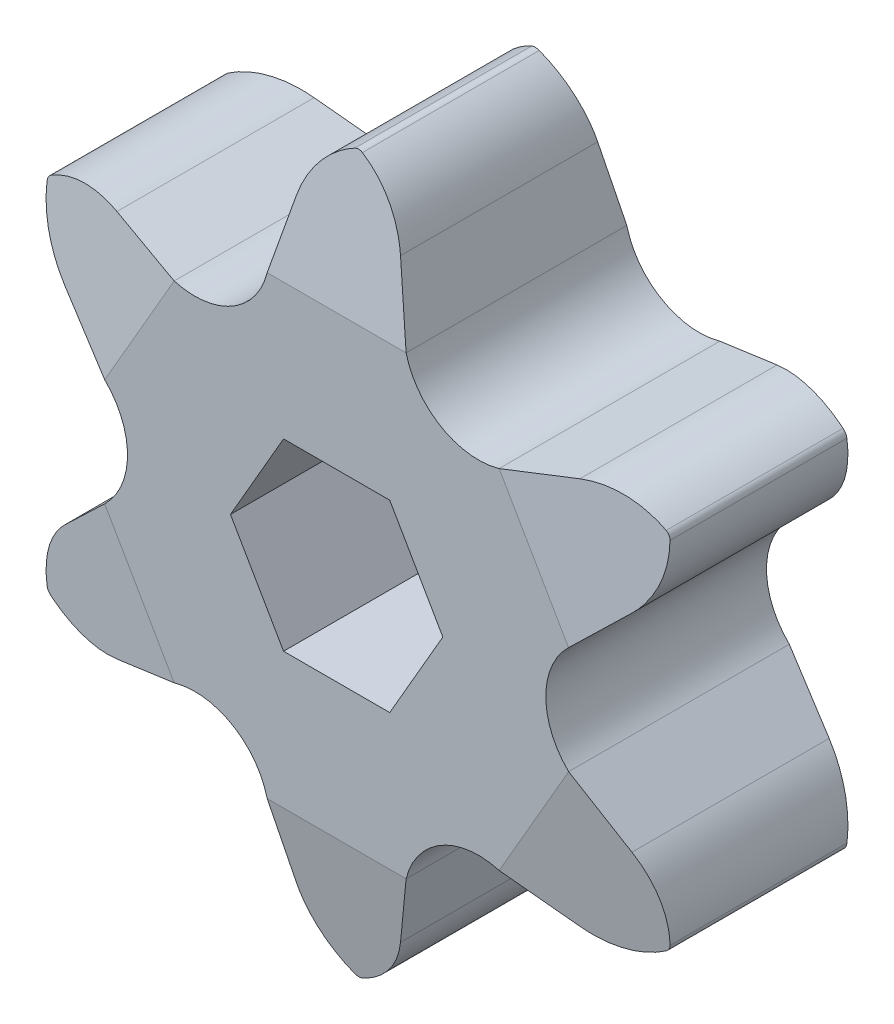
SolidWorks part; units mm, degrees
ref_plane "Front Plane" through (0, 0, 0) normal (0, 0, 1) x (1, 0, 0)
ref_plane "Top Plane" through (0, 0, 0) normal (0, 1, 0) x (1, 0, 0)
ref_plane "Right Plane" through (0, 0, 0) normal (1, 0, 0) x (0, 0, -1)
sketch "Sketch1" plane through (0, 0, 0) normal (0, 0, 1) x (1, 0, 0)
  line L0 (-5.0267, 5.911) -> (-7.4077, 6.5937)
  line L1 (-9.2066, 3.4779) -> (-7.4249, 1.7573)
  line L2 (2.9817, 7.7655) -> (2.3825, 10.1689)
  line L3 (-1.2153, 10.1689) -> (-1.8146, 7.7655)
  line L4 (8.592, 1.7573) -> (10.3738, 3.4779)
  line L5 (8.5749, 6.5937) -> (6.1938, 5.911)
  line L6 (6.1938, -6.1055) -> (8.5749, -6.7882)
  line L7 (10.3738, -3.6724) -> (8.592, -1.9518)
  line L8 (-1.8146, -7.96) -> (-1.2153, -10.3634)
  line L9 (2.3825, -10.3634) -> (2.9817, -7.96)
  line L10 (-7.4249, -1.9518) -> (-9.2066, -3.6724)
  line L11 (-7.4077, -6.7882) -> (-5.0267, -6.1055)
  arc A0 (-7.1314, 1.42) -> (-7.4249, 1.7573) centre (-9.2158, -0.0973) ccw
  arc A1 (-10.0364, 6.1886) -> (-10.1701, 5.9569) centre (-9.8707, 5.9385) ccw
  arc A2 (-4.5879, 5.8255) -> (-1.9599, 7.3427) centre (-4.3161, 8.3892) ccw
  arc A3 (-5.0267, 5.911) -> (-4.5879, 5.8255) centre (-4.3161, 8.3892) ccw
  arc A4 (-7.4077, 6.5937) -> (-10.0364, 6.1886) centre (-8.2829, 3.5417) ccw
  arc A5 (-10.1701, 5.9569) -> (-9.2066, 3.4779) centre (-7.0011, 5.7618) ccw
  arc A6 (-1.9599, 7.3427) -> (-1.8146, 7.7655) centre (-4.3161, 8.3892) ccw
  arc A7 (0.7173, 12.2428) -> (0.4498, 12.2428) centre (0.5836, 11.9742) ccw
  arc A8 (3.127, 7.3427) -> (5.755, 5.8255) centre (5.4832, 8.3892) ccw
  arc A9 (2.9817, 7.7655) -> (3.127, 7.3427) centre (5.4832, 8.3892) ccw
  arc A10 (2.3825, 10.1689) -> (0.7173, 12.2428) centre (-0.6982, 9.4008) ccw
  arc A11 (0.4498, 12.2428) -> (-1.2153, 10.1689) centre (1.8653, 9.4008) ccw
  arc A12 (5.755, 5.8255) -> (6.1938, 5.911) centre (5.4832, 8.3892) ccw
  arc A13 (11.3372, 5.9569) -> (11.2035, 6.1886) centre (11.0378, 5.9385) ccw
  arc A14 (8.2985, 1.42) -> (8.2985, -1.6145) centre (10.3829, -0.0973) ccw
  arc A15 (8.592, 1.7573) -> (8.2985, 1.42) centre (10.3829, -0.0973) ccw
  arc A16 (10.3738, 3.4779) -> (11.3372, 5.9569) centre (8.1682, 5.7618) ccw
  arc A17 (11.2035, 6.1886) -> (8.5749, 6.5937) centre (9.45, 3.5417) ccw
  arc A18 (8.2985, -1.6145) -> (8.592, -1.9518) centre (10.3829, -0.0973) ccw
  arc A19 (11.2035, -6.3831) -> (11.3372, -6.1514) centre (11.0378, -6.133) ccw
  arc A20 (5.755, -6.02) -> (3.127, -7.5373) centre (5.4832, -8.5837) ccw
  arc A21 (6.1938, -6.1055) -> (5.755, -6.02) centre (5.4832, -8.5837) ccw
  arc A22 (8.5749, -6.7882) -> (11.2035, -6.3831) centre (9.45, -3.7362) ccw
  arc A23 (11.3372, -6.1514) -> (10.3738, -3.6724) centre (8.1682, -5.9563) ccw
  arc A24 (3.127, -7.5373) -> (2.9817, -7.96) centre (5.4832, -8.5837) ccw
  arc A25 (0.4498, -12.4373) -> (0.7173, -12.4373) centre (0.5836, -12.1688) ccw
  arc A26 (-1.9599, -7.5373) -> (-4.5879, -6.02) centre (-4.3161, -8.5837) ccw
  arc A27 (-1.8146, -7.96) -> (-1.9599, -7.5373) centre (-4.3161, -8.5837) ccw
  arc A28 (-1.2153, -10.3634) -> (0.4498, -12.4373) centre (1.8653, -9.5953) ccw
  arc A29 (0.7173, -12.4373) -> (2.3825, -10.3634) centre (-0.6982, -9.5953) ccw
  arc A30 (-4.5879, -6.02) -> (-5.0267, -6.1055) centre (-4.3161, -8.5837) ccw
  arc A31 (-10.1701, -6.1514) -> (-10.0364, -6.3831) centre (-9.8707, -6.133) ccw
  arc A32 (-7.1314, -1.6145) -> (-7.1314, 1.42) centre (-9.2158, -0.0973) ccw
  arc A33 (-7.4249, -1.9518) -> (-7.1314, -1.6145) centre (-9.2158, -0.0973) ccw
  arc A34 (-9.2066, -3.6724) -> (-10.1701, -6.1514) centre (-7.0011, -5.9563) ccw
  arc A35 (-10.0364, -6.3831) -> (-7.4077, -6.7882) centre (-8.2829, -3.7362) ccw
  dimension "D1" = 2.5781
  dimension "D2" = 0.3
  dimension "D3" = 3.175
  dimension "D4" = 0.4498
  dimension "D5" = 0.5836
  dimension "D6" = 8.5749
  dimension "D7" = 8.592
  dimension "D8" = 11.0378
  dimension "D9" = 11.2035
  dimension "D10" = 1.9599
  dimension "D11" = 4.3161
  dimension "D12" = 7.0011
  dimension "D13" = 7.1314
  dimension "D14" = 3.4779
  dimension "D15" = 5.8255
extrude "Boss-Extrude1" add sketch "Sketch1" along normal mid plane 7.62
ref_plane "Plane1" through (0.5845, -0.0063, 0) normal (0.9999, -0.0108, 0) x (0, 0, -1)
ref_plane "Plane2" through (0.194, -0.3278, 0) normal (-0.5094, 0.8606, 0) x (0.8606, 0.5094, 0)
ref_axis "Axis1" through (0.5836, -0.0973, -4.191) along (0, 0, 1)
sketch "Sketch2" plane through (0, 0, 0) normal (1, 0, 0) x (0, 0, -1)
  line L0 (-3.048, 12.2742) -> (-3.81, 7.7655)
  line L1 (3.81, 12.2742) -> (-3.81, 12.2742) construction
  line L2 (-3.81, 7.7655) -> (-3.81, 12.2742)
  line L3 (-3.81, 12.2742) -> (-3.048, 12.2742)
  dimension "D1" = 0.762
extrude "Cut-Extrude1" cut sketch "Sketch2" against normal through all both and the other way through all
pattern_circular "CirPattern1" count 6 over 360 about axis through (0.5836, -0.0973, -4.191) along (0, 0, 1) of "Cut-Extrude1"
mirror "Mirror1" about plane through (0, 0, 0) normal (0, 0, 1) of "Cut-Extrude1", "CirPattern1"
sketch "Sketch4" plane through (0, 0, 3.81) normal (0, 0, 1) x (1, 0, 0)
  circle A0 centre (0.5836, -0.0973) radius 4.7625
  dimension "D1" = 9.525
extrude "Boss-Extrude2" [suppressed] add sketch "Sketch4" along normal mid plane 6.35
chamfer "Chamfer1" [suppressed] distance 3.175 distance2 1.27
sketch "Sketch3" plane through (0, 0, -3.81) normal (0, 0, -1) x (-1, 0, 0)
  line L1 (1.2495, -3.2723) -> (3.0826, -0.0973)
  line L2 (3.0826, -0.0973) -> (1.2495, 3.0777)
  line L3 (1.2495, 3.0777) -> (-2.4166, 3.0777)
  line L4 (-2.4166, 3.0777) -> (-4.2497, -0.0973)
  line L5 (-4.2497, -0.0973) -> (-2.4166, -3.2723)
  line L6 (-2.4166, -3.2723) -> (1.2495, -3.2723)
  circle A0 centre (-0.5836, -0.0973) radius 3.175 construction
  point P1 (0, 0)
  point P9 (-2.1501, -1.9619)
  point P11 (1.8637, 0)
  point P12 (0, 0)
  dimension "D1" = 6.35
extrude "Cut-Extrude2" cut sketch "Sketch3" against normal through all both and the other way through all
